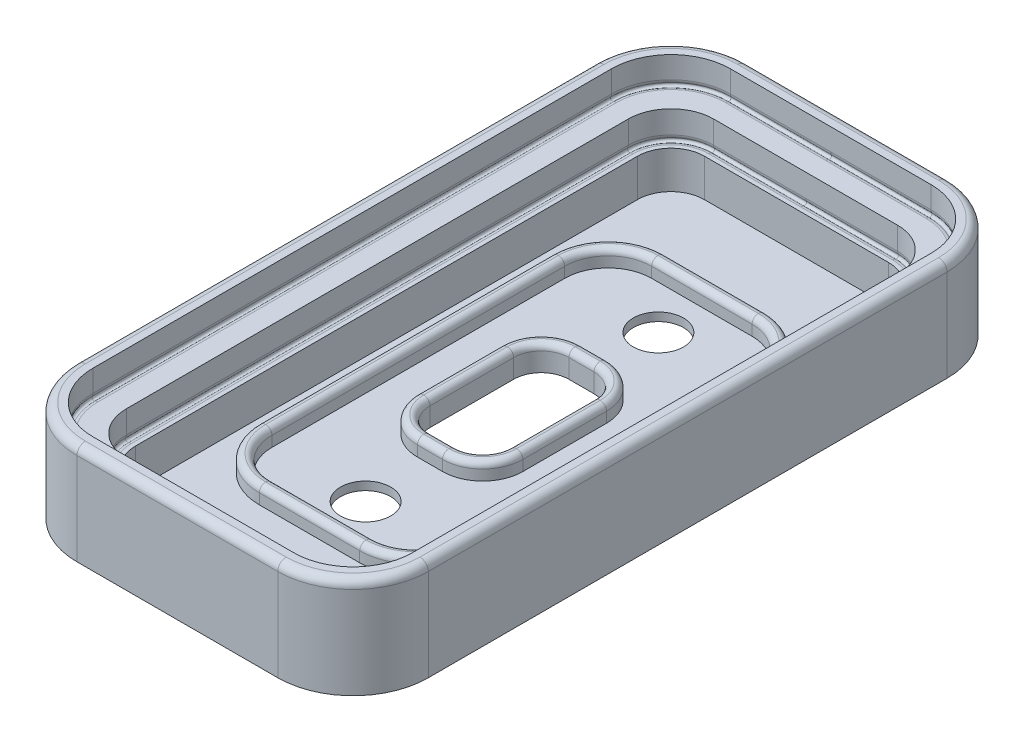
SolidWorks part; units mm, degrees
material "EN8"
ref_plane "Front Plane" through (0, 0, 0) normal (0, 0, 1) x (1, 0, 0)
ref_plane "Top Plane" through (0, 0, 0) normal (0, 1, 0) x (1, 0, 0)
ref_plane "Right Plane" through (0, 0, 0) normal (1, 0, 0) x (0, 0, -1)
sketch "Sketch1" plane through (0, 0, 0) normal (0, 1, 0) x (1, 0, 0)
  line L1 (-12, -40) -> (12, -40)
  line L2 (-21, -31) -> (-21, 31)
  line L3 (-12, 40) -> (12, 40)
  line L4 (21, -31) -> (21, 31)
  line L5 (-21, -40) -> (21, 40) construction
  line L6 (-21, 40) -> (21, -40) construction
  line L7 (16, -35) -> (-16, -35) construction
  line L8 (16, -35) -> (16, 35) construction
  line L9 (16, 35) -> (-16, 35) construction
  line L10 (-16, -35) -> (-16, 35) construction
  line L11 (16, -35) -> (-16, 35) construction
  line L12 (16, 35) -> (-16, -35) construction
  arc A0 (-12, -40) -> (-21, -31) centre (-12, -31) cw
  arc A1 (12, -40) -> (21, -31) centre (12, -31) ccw
  arc A2 (12, 40) -> (21, 31) centre (12, 31) cw
  arc A3 (-21, 31) -> (-12, 40) centre (-12, 31) cw
  point P0 (0, 0)
  point P18 (0, 0)
  dimension "D1" = 9
  dimension "D2" = 5
  dimension "D3" = 32
  dimension "D4" = 70
  dimension "D5" = 5
extrude "Boss-Extrude1" add sketch "Sketch1" along normal blind 8.8
ref_plane "Plane1" through (0, 1, 0) normal (0, 1, 0) x (1, 0, 0)
ref_plane "Plane2" through (0, 5.5, 0) normal (0, 1, 0) x (1, 0, 0)
sketch "Sketch4" plane through (0, 5.5, 0) normal (0, -1, 0) x (-1, 0, 0)
  line L0 (-16, -30) -> (-16, 30)
  line L1 (-11, -35) -> (11, -35) construction
  line L2 (-16, -30) -> (-16, 30) construction
  line L3 (-11, 35) -> (11, 35) construction
  line L4 (16, -30) -> (16, 30) construction
  line L5 (-16, -35) -> (16, 35) construction
  line L6 (-16, 35) -> (16, -35) construction
  line L7 (-11, 35) -> (11, 35)
  line L8 (16, -30) -> (16, 30)
  line L9 (-11, -35) -> (11, -35)
  arc A0 (-11, -35) -> (-16, -30) centre (-11, -30) cw construction
  arc A1 (11, -35) -> (16, -30) centre (11, -30) ccw construction
  arc A2 (11, 35) -> (16, 30) centre (11, 30) cw construction
  arc A3 (-16, 30) -> (-11, 35) centre (-11, 30) cw construction
  arc A4 (-16, 30) -> (-11, 35) centre (-11, 30) cw
  arc A5 (11, 35) -> (16, 30) centre (11, 30) cw
  arc A6 (11, -35) -> (16, -30) centre (11, -30) ccw
  arc A7 (-11, -35) -> (-16, -30) centre (-11, -30) cw
  point P0 (0, 0)
  dimension "D3" = 5
  dimension "D1" = 32
  dimension "D2" = 70
  dimension "D4" = 0
extrude "Cut-Extrude3" cut sketch "Sketch4" against normal through all
sketch "Sketch6" plane through (0, 1, 0) normal (0, 1, 0) x (1, 0, 0)
  line L8 (-11, -34) -> (11, -34)
  line L10 (-15, 30) -> (-15, -30)
  line L16 (11, 34) -> (-11, 34)
  line L18 (15, -30) -> (15, 30)
  line L20 (-11, -34) -> (11, -34)
  line L21 (-15, 30) -> (-15, -30)
  line L22 (11, 34) -> (-11, 34)
  line L23 (15, -30) -> (15, 30)
  arc A12 (11, -34) -> (15, -30) centre (11, -30) ccw
  arc A13 (-15, -30) -> (-11, -34) centre (-11, -30) ccw
  arc A14 (-11, 34) -> (-15, 30) centre (-11, 30) ccw
  arc A15 (15, 30) -> (11, 34) centre (11, 30) ccw
  arc A16 (11, -34) -> (15, -30) centre (11, -30) ccw
  arc A17 (-15, -30) -> (-11, -34) centre (-11, -30) ccw
  arc A18 (-11, 34) -> (-15, 30) centre (-11, 30) ccw
  arc A19 (15, 30) -> (11, 34) centre (11, 30) ccw
  dimension "D1" = 1
extrude "Cut-Extrude4" cut sketch "Sketch6" along normal through all
sketch "Sketch7" plane through (0, 1, 0) normal (0, 1, 0) x (1, 0, 0)
  line L0 (0, 17.5) -> (0, -17.5) construction
  line L1 (-1.5, -10) -> (1.5, -10)
  line L2 (-6.5, -5) -> (-6.5, 5)
  line L3 (-1.5, 10) -> (1.5, 10)
  line L4 (6.5, -5) -> (6.5, 5)
  line L5 (-6.5, -10) -> (6.5, 10) construction
  line L6 (-6.5, 10) -> (6.5, -10) construction
  line L7 (6, 22.5) -> (-6, 22.5)
  line L8 (11, 17.5) -> (11, -17.5)
  line L9 (6, -22.5) -> (-6, -22.5)
  line L10 (-11, 17.5) -> (-11, -17.5)
  line L11 (11, 22.5) -> (-11, -22.5) construction
  line L12 (11, -22.5) -> (-11, 22.5) construction
  arc A0 (-1.5, -10) -> (-6.5, -5) centre (-1.5, -5) cw
  arc A1 (1.5, -10) -> (6.5, -5) centre (1.5, -5) ccw
  arc A2 (1.5, 10) -> (6.5, 5) centre (1.5, 5) cw
  arc A3 (-6.5, 5) -> (-1.5, 10) centre (-1.5, 5) cw
  arc A4 (-6, -22.5) -> (-11, -17.5) centre (-6, -17.5) cw
  arc A5 (11, -17.5) -> (6, -22.5) centre (6, -17.5) cw
  arc A6 (6, 22.5) -> (11, 17.5) centre (6, 17.5) cw
  arc A7 (-6, 22.5) -> (-11, 17.5) centre (-6, 17.5) ccw
  circle A8 centre (0, 17.5) radius 2.5
  circle A9 centre (0, -17.5) radius 2.5
  point P0 (0, 0)
  point P18 (0, 0)
  dimension "D3" = 5
  dimension "D6" = 5
  dimension "D8" = 5
  dimension "D1" = 13
  dimension "D2" = 20
  dimension "D4" = 22
  dimension "D5" = 45
  dimension "D7" = 5
sketch "Sketch8" plane through (0, 1, 0) normal (0, 1, 0) x (1, 0, 0)
  line L4 (1.5, 8.3) -> (-1.5, 8.3)
  line L5 (-4.8, 5) -> (-4.8, -5)
  line L6 (-1.5, -8.3) -> (1.5, -8.3)
  line L7 (4.8, -5) -> (4.8, 5)
  line L8 (-1.5, -9.8) -> (1.5, -9.8)
  line L9 (6.3, -5) -> (6.3, 5)
  line L10 (-6.3, 5) -> (-6.3, -5)
  line L11 (1.5, 9.8) -> (-1.5, 9.8)
  line L12 (-1.5, -9.8) -> (1.5, -9.8)
  line L13 (6.3, -5) -> (6.3, 5)
  line L14 (-6.3, 5) -> (-6.3, -5)
  line L15 (1.5, 9.8) -> (-1.5, 9.8)
  line L20 (-6, -24.2) -> (6, -24.2)
  line L21 (12.7, -17.5) -> (12.7, 17.5)
  line L22 (6, 24.2) -> (-6, 24.2)
  line L23 (-12.7, 17.5) -> (-12.7, -17.5)
  line L24 (-6, -22.7) -> (6, -22.7)
  line L25 (11.2, -17.5) -> (11.2, 17.5)
  line L26 (-11.2, 17.5) -> (-11.2, -17.5)
  line L27 (6, 22.7) -> (-6, 22.7)
  line L28 (-6, -22.7) -> (6, -22.7)
  line L29 (11.2, -17.5) -> (11.2, 17.5)
  line L30 (-11.2, 17.5) -> (-11.2, -17.5)
  line L31 (6, 22.7) -> (-6, 22.7)
  arc A4 (4.8, 5) -> (1.5, 8.3) centre (1.5, 5) ccw
  arc A5 (-1.5, 8.3) -> (-4.8, 5) centre (-1.5, 5) ccw
  arc A6 (-4.8, -5) -> (-1.5, -8.3) centre (-1.5, -5) ccw
  arc A7 (1.5, -8.3) -> (4.8, -5) centre (1.5, -5) ccw
  arc A8 (-6.3, -5) -> (-1.5, -9.8) centre (-1.5, -5) ccw
  arc A9 (1.5, -9.8) -> (6.3, -5) centre (1.5, -5) ccw
  arc A10 (6.3, 5) -> (1.5, 9.8) centre (1.5, 5) ccw
  arc A11 (-1.5, 9.8) -> (-6.3, 5) centre (-1.5, 5) ccw
  arc A12 (-6.3, -5) -> (-1.5, -9.8) centre (-1.5, -5) ccw
  arc A13 (1.5, -9.8) -> (6.3, -5) centre (1.5, -5) ccw
  arc A14 (6.3, 5) -> (1.5, 9.8) centre (1.5, 5) ccw
  arc A15 (-1.5, 9.8) -> (-6.3, 5) centre (-1.5, 5) ccw
  arc A20 (-12.7, -17.5) -> (-6, -24.2) centre (-6, -17.5) ccw
  arc A21 (6, -24.2) -> (12.7, -17.5) centre (6, -17.5) ccw
  arc A22 (12.7, 17.5) -> (6, 24.2) centre (6, 17.5) ccw
  arc A23 (-6, 24.2) -> (-12.7, 17.5) centre (-6, 17.5) ccw
  arc A24 (-11.2, -17.5) -> (-6, -22.7) centre (-6, -17.5) ccw
  arc A25 (6, -22.7) -> (11.2, -17.5) centre (6, -17.5) ccw
  arc A26 (11.2, 17.5) -> (6, 22.7) centre (6, 17.5) ccw
  arc A27 (-6, 22.7) -> (-11.2, 17.5) centre (-6, 17.5) ccw
  arc A28 (-11.2, -17.5) -> (-6, -22.7) centre (-6, -17.5) ccw
  arc A29 (6, -22.7) -> (11.2, -17.5) centre (6, -17.5) ccw
  arc A30 (11.2, 17.5) -> (6, 22.7) centre (6, 17.5) ccw
  arc A31 (-6, 22.7) -> (-11.2, 17.5) centre (-6, 17.5) ccw
  circle A38 centre (0, 17.5) radius 3
  circle A39 centre (0, 17.5) radius 3
  circle A41 centre (0, -17.5) radius 3
  circle A42 centre (0, -17.5) radius 3
  dimension "D1" = 0.2
  dimension "D2" = 1.5
  dimension "D3" = 0.2
  dimension "D4" = 1.5
  dimension "D5" = 0.5
  dimension "D6" = 0.5
extrude "Boss-Extrude2" add sketch "Sketch8" along normal blind 2 contours L22 A23 L23 A20 L20 A21 L21 A22 A31 L31 A30 L29 A29 L28 A28 L30 | L15 A15 L14 A12 L12 A13 L13 A14 A7 L6 A6 L5 A5 L4 A4 L7 region at (-4.7294, 1, 8.2294) region at (-10.3511, 1, 21.8511)
extrude "Cut-Extrude5" cut sketch "Sketch8<3>" against normal blind 2 contours L6 A7 L7 A4 L4 A5 L5 A6 | A39 | A42 region at (0, 1, 0) region at (0, 1, -17.5) region at (0, 1, 17.5)
sketch "Sketch8<3>" plane through (0, 1, 0) normal (0, 1, 0) x (1, 0, 0) same geometry as "Sketch8"
fillet "Fillet1" radius 0.75 32 edges at (10.7376, 3, -22.2376) (12.7, 3, 0) (10.7376, 3, 22.2376) (0, 3, 24.2) (-10.7376, 3, 22.2376) (-12.7, 3, 0) (-10.7376, 3, -22.2376) (0, 3, -24.2) (-11.2, 3, 0) (-9.677, 3, 21.177) (0, 3, 22.7) (9.677, 3, 21.177) (11.2, 3, 0) (9.677, 3, -21.177) (0, 3, -22.7) (-9.677, 3, -21.177) (4.8941, 3, -8.3941) (6.3, 3, 0) (4.8941, 3, 8.3941) (0, 3, 9.8) (-4.8941, 3, 8.3941) (-6.3, 3, 0) (-4.8941, 3, -8.3941) (0, 3, -9.8) (4.8, 3, 0) (3.8335, 3, -7.3335) (0, 3, -8.3) (-3.8335, 3, -7.3335) (-4.8, 3, 0) (-3.8335, 3, 7.3335) (0, 3, 8.3) (3.8335, 3, 7.3335)
sketch "Sketch9" plane through (0, 8.8, 0) normal (0, 1, 0) x (1, 0, 0)
  line L8 (-12, -38) -> (12, -38)
  line L9 (19, -31) -> (19, 31)
  line L10 (-19, 31) -> (-19, -31)
  line L11 (12, 38) -> (-12, 38)
  line L12 (-12, -38) -> (12, -38)
  line L13 (19, -31) -> (19, 31)
  line L14 (-19, 31) -> (-19, -31)
  line L15 (12, 38) -> (-12, 38)
  line L16 (-12, -40) -> (12, -40)
  line L17 (21, -31) -> (21, 31)
  line L18 (12, 40) -> (-12, 40)
  line L19 (-21, 31) -> (-21, -31)
  line L20 (-12, -40) -> (12, -40)
  line L21 (21, -31) -> (21, 31)
  line L22 (12, 40) -> (-12, 40)
  line L23 (-21, 31) -> (-21, -31)
  arc A8 (-19, -31) -> (-12, -38) centre (-12, -31) ccw
  arc A9 (12, -38) -> (19, -31) centre (12, -31) ccw
  arc A10 (19, 31) -> (12, 38) centre (12, 31) ccw
  arc A11 (-12, 38) -> (-19, 31) centre (-12, 31) ccw
  arc A12 (-19, -31) -> (-12, -38) centre (-12, -31) ccw
  arc A13 (12, -38) -> (19, -31) centre (12, -31) ccw
  arc A14 (19, 31) -> (12, 38) centre (12, 31) ccw
  arc A15 (-12, 38) -> (-19, 31) centre (-12, 31) ccw
  arc A16 (-21, -31) -> (-12, -40) centre (-12, -31) ccw
  arc A17 (12, -40) -> (21, -31) centre (12, -31) ccw
  arc A18 (21, 31) -> (12, 40) centre (12, 31) ccw
  arc A19 (-12, 40) -> (-21, 31) centre (-12, 31) ccw
  arc A20 (-21, -31) -> (-12, -40) centre (-12, -31) ccw
  arc A21 (12, -40) -> (21, -31) centre (12, -31) ccw
  arc A22 (21, 31) -> (12, 40) centre (12, 31) ccw
  arc A23 (-12, 40) -> (-21, 31) centre (-12, 31) ccw
  dimension "D1" = 2
  dimension "D2" = 0
extrude "Boss-Extrude3" add sketch "Sketch9" along normal blind 3.2
fillet "Fillet3" radius 1 8 edges at (21, 12, 0) (18.364, 12, 37.364) (0, 12, 40) (-18.364, 12, 37.364) (-21, 12, 0) (-18.364, 12, -37.364) (0, 12, -40) (18.364, 12, -37.364)
sketch "Sketch10" plane through (0, 0, 0) normal (1, 0, 0) x (0, 0, -1)
  line L0 (-30, 5.5) -> (30, 5.5) construction
  line L1 (-30, 5.5) -> (30, 5.5) construction
  line L2 (-30, 8.8) -> (30, 8.8) construction
  line L3 (-30, 8.8) -> (30, 8.8) construction
  line L4 (-25, 8.8) -> (-25, 5.5) construction
  circle A0 centre (-25, 7.15) radius 1.5
  point P4 (0, 0)
  dimension "D1" = 3
  dimension "D2" = 25
sketch "Sketch11" plane through (0, 5.5, 0) normal (0, 1, 0) x (1, 0, 0)
  line L0 (16.1, -30) -> (16.1, 30)
  line L1 (11, 35.1) -> (-11, 35.1)
  line L2 (-16.1, 30) -> (-16.1, -30)
  line L3 (-11, -35.1) -> (11, -35.1)
  line L4 (16, -30) -> (16, 30)
  line L5 (11, 35) -> (-11, 35)
  line L6 (-16, 30) -> (-16, -30)
  line L7 (-11, -35) -> (11, -35)
  line L8 (16, -30) -> (16, 30)
  line L9 (11, 35) -> (-11, 35)
  line L10 (-16, 30) -> (-16, -30)
  line L11 (-11, -35) -> (11, -35)
  arc A0 (16.1, 30) -> (11, 35.1) centre (11, 30) ccw
  arc A1 (-11, 35.1) -> (-16.1, 30) centre (-11, 30) ccw
  arc A2 (-16.1, -30) -> (-11, -35.1) centre (-11, -30) ccw
  arc A3 (11, -35.1) -> (16.1, -30) centre (11, -30) ccw
  arc A4 (11, -35) -> (16, -30) centre (11, -30) ccw
  arc A5 (16, 30) -> (11, 35) centre (11, 30) ccw
  arc A6 (-11, 35) -> (-16, 30) centre (-11, 30) ccw
  arc A7 (-16, -30) -> (-11, -35) centre (-11, -30) ccw
  arc A8 (11, -35) -> (16, -30) centre (11, -30) ccw
  arc A9 (16, 30) -> (11, 35) centre (11, 30) ccw
  arc A10 (-11, 35) -> (-16, 30) centre (-11, 30) ccw
  arc A11 (-16, -30) -> (-11, -35) centre (-11, -30) ccw
  dimension "D1" = 0
  dimension "D2" = 0.1
extrude "Cut-Extrude7" cut sketch "Sketch11" along normal through all
sketch "Sketch12" plane through (0, 8.8, 0) normal (0, 1, 0) x (1, 0, 0)
  line L0 (-19.1, 31) -> (-19.1, -31)
  line L1 (-12, -38.1) -> (12, -38.1)
  line L2 (19.1, -31) -> (19.1, 31)
  line L3 (12, 38.1) -> (-12, 38.1)
  line L4 (-19, 31) -> (-19, -31)
  line L5 (-12, -38) -> (12, -38)
  line L6 (19, -31) -> (19, 31)
  line L7 (12, 38) -> (-12, 38)
  line L8 (-19, 31) -> (-19, -31)
  line L9 (-12, -38) -> (12, -38)
  line L10 (19, -31) -> (19, 31)
  line L11 (12, 38) -> (-12, 38)
  arc A0 (-19.1, -31) -> (-12, -38.1) centre (-12, -31) ccw
  arc A1 (12, -38.1) -> (19.1, -31) centre (12, -31) ccw
  arc A2 (19.1, 31) -> (12, 38.1) centre (12, 31) ccw
  arc A3 (-12, 38.1) -> (-19.1, 31) centre (-12, 31) ccw
  arc A4 (-19, -31) -> (-12, -38) centre (-12, -31) ccw
  arc A5 (12, -38) -> (19, -31) centre (12, -31) ccw
  arc A6 (19, 31) -> (12, 38) centre (12, 31) ccw
  arc A7 (-12, 38) -> (-19, 31) centre (-12, 31) ccw
  arc A8 (-19, -31) -> (-12, -38) centre (-12, -31) ccw
  arc A9 (12, -38) -> (19, -31) centre (12, -31) ccw
  arc A10 (19, 31) -> (12, 38) centre (12, 31) ccw
  arc A11 (-12, 38) -> (-19, 31) centre (-12, 31) ccw
  dimension "D1" = 0
  dimension "D2" = 0.1
extrude "Cut-Extrude8" cut sketch "Sketch12" along normal through all
sketch "Sketch13" plane through (0, 0, 0) normal (1, 0, 0) x (0, 0, -1)
  line L0 (36.1672, 8.8) -> (38.1, 8.8) construction
  line L2 (38.1, 8.8) -> (38.1, 9.966) construction
  line L3 (38.1, 12) -> (38.1, 8.8) construction
  line L4 (-30, 8.8) -> (-35.1, 8.8) construction
  line L5 (38.1, 8.8) -> (37.9586, 8.9414) construction
  circle A1 centre (37.9586, 8.9414) radius 0.25
  dimension "D1" = 45
  dimension "D2" = 0.5
  dimension "D3" = 0.2
sketch "Sketch14" plane through (0, 8.8, 0) normal (0, 1, 0) x (1, 0, 0)
  line L4 (-19.1, 31) -> (-19.1, -31)
  line L5 (-12, -38.1) -> (12, -38.1)
  line L6 (19.1, -31) -> (19.1, 31)
  line L7 (12, 38.1) -> (-12, 38.1)
  line L8 (-19.1, 31) -> (-19.1, -31)
  line L9 (-12, -38.1) -> (12, -38.1)
  line L10 (19.1, -31) -> (19.1, 31)
  line L11 (12, 38.1) -> (-12, 38.1)
  arc A4 (-12, 38.1) -> (-19.1, 31) centre (-12, 31) ccw
  arc A5 (-19.1, -31) -> (-12, -38.1) centre (-12, -31) ccw
  arc A6 (12, -38.1) -> (19.1, -31) centre (12, -31) ccw
  arc A7 (19.1, 31) -> (12, 38.1) centre (12, 31) ccw
  arc A8 (-12, 38.1) -> (-19.1, 31) centre (-12, 31) ccw
  arc A9 (-19.1, -31) -> (-12, -38.1) centre (-12, -31) ccw
  arc A10 (12, -38.1) -> (19.1, -31) centre (12, -31) ccw
  arc A11 (19.1, 31) -> (12, 38.1) centre (12, 31) ccw
  dimension "D1" = 0
sweep "Cut-Sweep1" cut profiles "Sketch13" path "Sketch14"
sketch "Sketch15" plane through (0, 0, 0) normal (1, 0, 0) x (0, 0, -1)
  line L0 (32.6053, 5.5) -> (35.1, 5.5) construction
  line L1 (35.1, 5.5) -> (35.1, 6.8847) construction
  line L3 (35.1, 8.8) -> (35.1, 5.5) construction
  line L4 (-30, 5.5) -> (-34, 5.5) construction
  line L5 (35.1, 5.5) -> (34.9586, 5.6414) construction
  circle A0 centre (34.9586, 5.6414) radius 0.25
  dimension "D2" = 0.5
  dimension "D1" = 45
  dimension "D3" = 0.2
sketch "Sketch16" plane through (0, 5.5, 0) normal (0, 1, 0) x (1, 0, 0)
  line L4 (16.1, -30) -> (16.1, 30)
  line L5 (11, 35.1) -> (-11, 35.1)
  line L6 (-16.1, 30) -> (-16.1, -30)
  line L7 (-11, -35.1) -> (11, -35.1)
  line L8 (16.1, -30) -> (16.1, 30)
  line L9 (11, 35.1) -> (-11, 35.1)
  line L10 (-16.1, 30) -> (-16.1, -30)
  line L11 (-11, -35.1) -> (11, -35.1)
  arc A4 (11, -35.1) -> (16.1, -30) centre (11, -30) ccw
  arc A5 (16.1, 30) -> (11, 35.1) centre (11, 30) ccw
  arc A6 (-11, 35.1) -> (-16.1, 30) centre (-11, 30) ccw
  arc A7 (-16.1, -30) -> (-11, -35.1) centre (-11, -30) ccw
  arc A8 (11, -35.1) -> (16.1, -30) centre (11, -30) ccw
  arc A9 (16.1, 30) -> (11, 35.1) centre (11, 30) ccw
  arc A10 (-11, 35.1) -> (-16.1, 30) centre (-11, 30) ccw
  arc A11 (-16.1, -30) -> (-11, -35.1) centre (-11, -30) ccw
  dimension "D1" = 0
sweep "Cut-Sweep2" cut profiles "Sketch15" path "Sketch16"
fillet "Fillet4" radius 0.75 36 edges at (-17.0205, 9.1476, -36.0205) (-19.1, 9.1476, 0) (-17.0205, 9.1476, 36.0205) (0, 9.1476, 38.1) (17.0205, 9.1476, 36.0205) (19.1, 9.1476, 0) (17.0205, 9.1476, -36.0205) (6, 9.1476, -38.1) (-16.7747, 8.8, -35.7747) (-18.7524, 8.8, 0) (-16.7747, 8.8, 35.7747) (0, 8.8, 37.7524) (16.7747, 8.8, 35.7747) (18.7524, 8.8, 0) (16.7747, 8.8, -35.7747) (6, 8.8, -37.7524) (-6, 9.1476, -38.1) (-6, 8.8, -37.7524) (-14.3605, 5.5, -33.3605) (-15.7524, 5.5, 0) (-14.3605, 5.5, 33.3605) (0, 5.5, 34.7524) (14.3605, 5.5, 33.3605) (15.7524, 5.5, 0) (14.3605, 5.5, -33.3605) (5.5, 5.5, -34.7524) (5.5, 5.8476, -35.1) (14.6062, 5.8476, -33.6062) (16.1, 5.8476, 0) (14.6062, 5.8476, 33.6062) (0, 5.8476, 35.1) (-14.6062, 5.8476, 33.6062) (-16.1, 5.8476, 0) (-14.6062, 5.8476, -33.6062) (-5.5, 5.5, -34.7524) (-5.5, 5.8476, -35.1)
